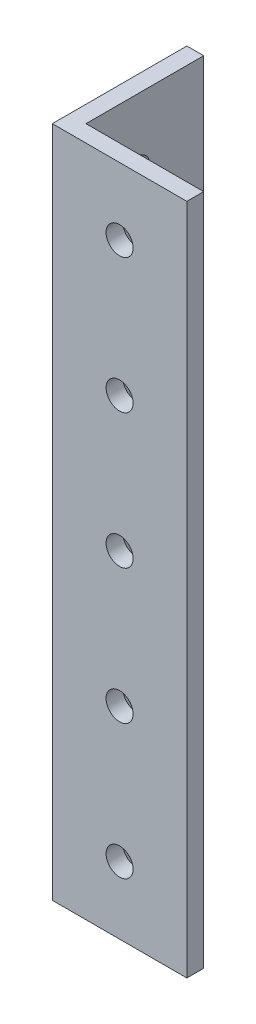
SolidWorks part; units mm, degrees
ref_plane "Front Plane" through (0, 0, 0) normal (0, 0, 1) x (1, 0, 0)
ref_plane "Top Plane" through (0, 0, 0) normal (0, 1, 0) x (1, 0, 0)
ref_plane "Right Plane" through (0, 0, 0) normal (1, 0, 0) x (0, 0, -1)
sketch "Sketch2" plane through (0, 0, 0) normal (0, 1, 0) x (1, 0, 0)
  line L1 (-20.6198, -0.4952) -> (4.7802, -0.4952)
  line L2 (-20.6198, -0.4952) -> (-20.6198, 24.9048)
  line L3 (-20.6198, 24.9048) -> (4.7802, 24.9048)
  line L4 (4.7802, -0.4952) -> (4.7802, 24.9048)
  line L5 (-20.6198, -0.4952) -> (4.7802, 24.9048) construction
  line L6 (-20.6198, 24.9048) -> (4.7802, -0.4952) construction
  line L7 (-17.4448, 2.6798) -> (4.7802, 2.6798)
  line L8 (-17.4448, 2.6798) -> (-17.4448, 24.9048)
  line L9 (-17.4448, 24.9048) -> (4.7802, 24.9048)
  line L10 (4.7802, 2.6798) -> (4.7802, 24.9048)
  line L11 (-17.4448, 2.6798) -> (4.7802, 24.9048) construction
  line L12 (-17.4448, 24.9048) -> (4.7802, 2.6798) construction
  point P0 (-7.9198, 12.2048)
  point P5 (-6.3323, 13.7923)
  dimension "D1" = 25.4
  dimension "D2" = 25.4
  dimension "D3" = 22.225
  dimension "D4" = 22.225
  dimension "D5" = 3.175
  dimension "D6" = 3.175
extrude "Boss-Extrude1" add sketch "Sketch2" along normal blind 127 contours L7 L8 L3 L2 L1 L4 region at (-20.2606, 0, -12.2048)
sketch "Sketch3" plane through (-17.4448, 0, 0) normal (1, 0, 0) x (0, 0, -1)
  line L0 (2.6798, 0) -> (24.9048, 0) construction
  line L1 (24.9048, 127) -> (24.9048, 0) construction
  circle A0 centre (12.2048, 12.7) radius 2.5527
  dimension "D1" = 5.1054
  dimension "D2" = 12.7
  dimension "D3" = 12.7
extrude "Cut-Extrude1" cut sketch "Sketch3" against normal through all
pattern_linear "LPattern1" count 5 spacing 25.4 along (0, 1, 0) of "Cut-Extrude1"
sketch "Sketch4" plane through (0, 0, -2.6798) normal (0, 0, -1) x (-1, 0, 0)
  line L0 (17.4448, 0) -> (-4.7802, 0) construction
  line L1 (-4.7802, 127) -> (-4.7802, 0) construction
  circle A0 centre (7.9198, 12.7) radius 2.5527
  dimension "D1" = 5.1054
  dimension "D2" = 12.7
  dimension "D3" = 12.7
extrude "Cut-Extrude2" cut sketch "Sketch4" against normal through all
pattern_linear "LPattern2" count 5 spacing 25.4 along (0, 1, 0) of "Cut-Extrude2"
